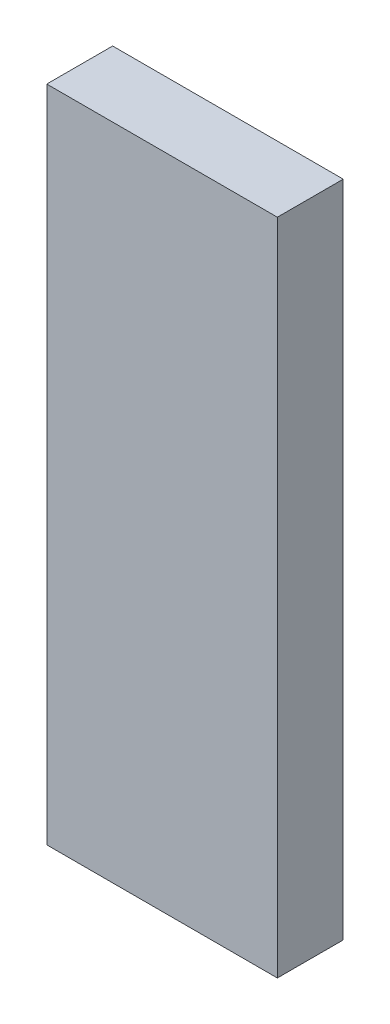
SolidWorks part; units mm, degrees
ref_plane "Front Plane" through (0, 0, 0) normal (0, 0, 1) x (1, 0, 0)
ref_plane "Top Plane" through (0, 0, 0) normal (0, 1, 0) x (1, 0, 0)
ref_plane "Right Plane" through (0, 0, 0) normal (1, 0, 0) x (0, 0, -1)
sketch "Sketch1" plane through (0, 0, 0) normal (0, 0, 1) x (1, 0, 0)
  line L1 (-3.5, 10) -> (3.5, 10)
  line L2 (-3.5, 10) -> (-3.5, -10)
  line L3 (-3.5, -10) -> (3.5, -10)
  line L4 (3.5, 10) -> (3.5, -10)
  line L5 (-3.5, 10) -> (3.5, -10) construction
  line L6 (-3.5, -10) -> (3.5, 10) construction
  point P0 (0, 0)
  dimension "D1" = 7
  dimension "D2" = 20
extrude "Boss-Extrude1" add sketch "Sketch1" along normal blind 2
